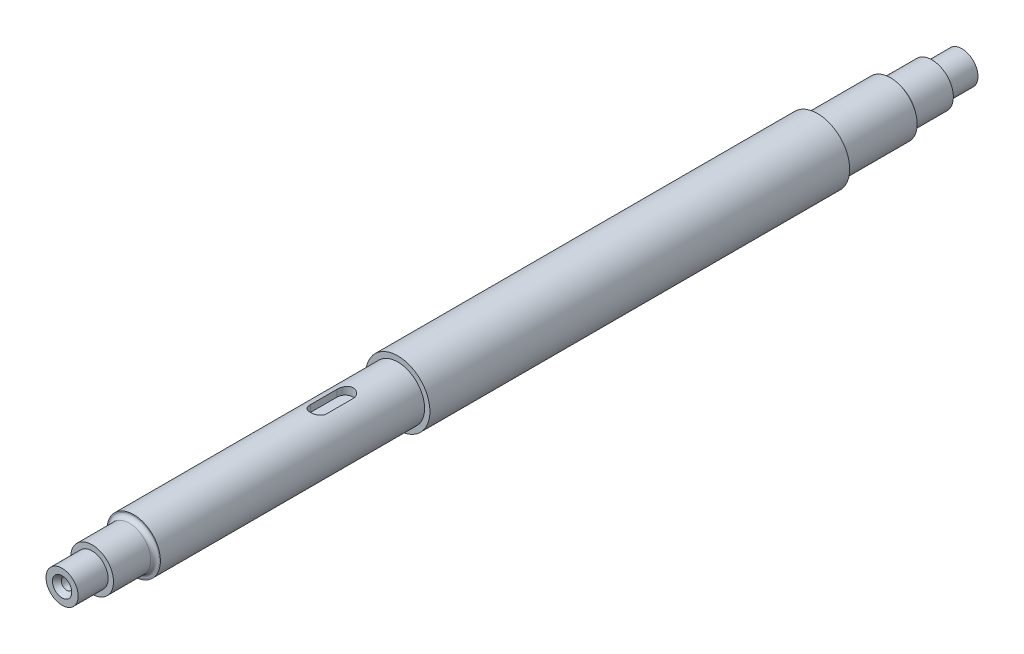
SolidWorks part; units mm, degrees
material "Alloy Steel"
ref_plane "Front Plane" through (0, 0, 0) normal (0, 0, 1) x (1, 0, 0)
ref_plane "Top Plane" through (0, 0, 0) normal (0, 1, 0) x (1, 0, 0)
ref_plane "Right Plane" through (0, 0, 0) normal (1, 0, 0) x (0, 0, -1)
sketch "Sketch1" plane through (0, 0, 0) normal (0, 0, 1) x (1, 0, 0)
  circle A0 centre (0, 0) radius 9.525
  dimension "D1" = 19.05
extrude "Boss-Extrude1" add sketch "Sketch1" along normal mid plane 279.4
ref_plane "Plane1" through (0, 0, 90.551) normal (0, 0, 1) x (1, 0, 0)
sketch "Sketch3" plane through (0, 0, 90.551) normal (0, 0, 1) x (1, 0, 0)
  circle A0 centre (0, 0) radius 7.9375
  circle A1 centre (0, 0) radius 9.525
  circle A2 centre (0, 0) radius 9.525
  dimension "D2" = 15.875
  dimension "D1" = 0
extrude "Cut-Extrude1" cut sketch "Sketch3" along normal up to next
mirror "Mirror1" about plane through (0, 0, 0) normal (0, 0, 1) of "Cut-Extrude1"
ref_plane "Plane2" through (0, 0, 124.46) normal (0, 0, 1) x (1, 0, 0)
sketch "Sketch4" plane through (0, 0, 124.46) normal (0, 0, 1) x (1, 0, 0)
  circle A0 centre (0, 0) radius 4.7625
  circle A1 centre (0, 0) radius 7.9375
  circle A2 centre (0, 0) radius 7.9375
  dimension "D2" = 9.525
  dimension "D1" = 0
extrude "Cut-Extrude2" cut sketch "Sketch4" along normal up to next
mirror "Mirror2" about plane through (0, 0, 0) normal (0, 0, 1) of "Cut-Extrude2"
sketch "Sketch5" plane through (0, 0, 90.551) normal (0, 0, 1) x (1, 0, 0)
  circle A0 centre (0, 0) radius 9.525 construction
  circle A1 centre (0, 0) radius 9.525
  circle A3 centre (0, 0) radius 7.9375 construction
  circle A4 centre (0, 0) radius 7.9375
extrude "Cut-Extrude3" cut sketch "Sketch5" against normal blind 58.6105
ref_plane "Plane3" through (0, 7.9375, 0) normal (0, 1, 0) x (1, 0, 0)
sketch "Sketch6" plane through (0, 7.9375, 0) normal (0, 1, 0) x (1, 0, 0)
  line L0 (-9.525, -31.9405) -> (9.525, -31.9405) construction
  line L2 (-9.525, -31.9405) -> (9.525, -31.9405)
  line L3 (-7.9375, -124.46) -> (7.9375, -124.46) construction
  line L4 (0, -90.551) -> (0, -31.9405) construction
  line L8 (0, -57.3722) -> (0, -49.4347) construction
  line L9 (-2.3812, -57.3722) -> (-2.3813, -49.4348)
  line L10 (2.3813, -57.3722) -> (2.3812, -49.4347)
  line L11 (0, -47.0535) -> (-5.2744, -47.0535) construction
  line L12 (0, -59.7535) -> (-5.6689, -59.7535) construction
  line L13 (-7.9375, -124.46) -> (7.9375, -124.46) construction
  arc A0 (-2.3812, -57.3722) -> (2.3813, -57.3722) centre (0, -57.3722) ccw
  arc A1 (2.3812, -49.4347) -> (-2.3813, -49.4348) centre (0, -49.4347) ccw
  point P14 (0, -53.4035)
  dimension "D1" = 4.7625
  dimension "D2" = 12.7
  dimension "D3" = 37.1475
  dimension "D4" = 33.909
extrude "Cut-Extrude4" cut sketch "Sketch6" against normal blind 2.3812 contours L10 A1 L9 A0 region at (0, 7.9375, 53.4035)
sketch "Sketch7" plane through (0, 0, 124.46) normal (0, 0, 1) x (1, 0, 0)
  circle A0 centre (0, 0) radius 7.9375 construction
  circle A1 centre (0, 0) radius 7.9375
  circle A2 centre (0, 0) radius 6.35
  dimension "D1" = 12.7
extrude "Cut-Extrude5" cut sketch "Sketch7" against normal blind 12.319
fillet "Fillet1" radius 1.27 1 edges at (6.35, 0, 112.141)
sketch "Sketch8" plane through (0, 0, 139.7) normal (0, 0, 1) x (1, 0, 0)
  circle A0 centre (0, 0) radius 4.7625 construction
  circle A1 centre (0, 0) radius 4.7625
extrude "Cut-Extrude6" cut sketch "Sketch8" against normal blind 6.35
sketch "Sketch9" plane through (0, 0, 133.35) normal (0, 0, 1) x (1, 0, 0)
  circle A0 centre (0, 0) radius 4.7625 construction
  circle A1 centre (0, 0) radius 4.7625
  point P4 (0, 0)
hole_wizard "CSK for #4 Flat Head Machine Screw1" positions "3DSketch1" profile "Sketch10" countersink size "#4" standard "ANSI Inch"
sketch3d "3DSketch1"
  point P0 (0, 0, 133.35)
sketch "Sketch10" plane through (0, 0, 133.35) normal (1, 0, 0) x (0, -1, 0)
  line L0 (0, 0) -> (0, 7.3306)
  line L1 (0, 7.3306) -> (1.6319, 6.35)
  line L2 (1.6319, 6.35) -> (1.6319, 1.4098)
  line L3 (1.6319, 1.4098) -> (2.8575, 0)
  line L5 (2.8575, 0) -> (0, 0)
  line L6 (-1.6319, 1.4098) -> (-2.8575, 0) construction
  line L10 (0, 7.3306) -> (-1.6319, 6.35) construction
  line L11 (0, -6.35) -> (0, 107.95) construction
  dimension "Hole Dia." = 3.2639
  dimension "Hole Depth" = 6.35
  dimension "Near C'Sink Dia." = 5.715
  dimension "Near C'Sink Angle" = 82
  dimension "Drill Angle" = 118
mirror "Mirror3" about plane through (0, 0, 0) normal (0, 0, 1) of "CSK for #4 Flat Head Machine Screw1", "Fillet1", "Cut-Extrude5", "Cut-Extrude6"
sketch "Sketch11" plane through (0, 0, 31.9405) normal (0, 0, 1) x (1, 0, 0)
  circle A0 centre (0, 0) radius 7.9375 construction
  circle A1 centre (0, 0) radius 9.525 construction
  circle A2 centre (0, 0) radius 7.9375
  circle A3 centre (0, 0) radius 9.525
extrude "Boss-Extrude2" add sketch "Sketch11" along normal blind 1.905
